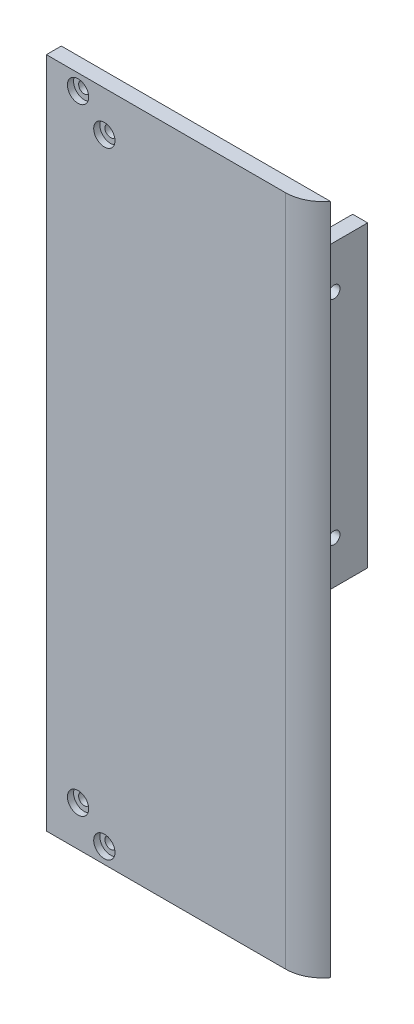
SolidWorks part; units mm, degrees
ref_plane "Alzado" through (0, 0, 0) normal (0, 0, 1) x (1, 0, 0)
ref_plane "Planta" through (0, 0, 0) normal (0, 1, 0) x (1, 0, 0)
ref_plane "Vista lateral" through (0, 0, 0) normal (1, 0, 0) x (0, 0, -1)
sketch "Croquis1" plane through (0, 0, 0) normal (0, 0, 1) x (1, 0, 0)
  line L1 (-4, 72.7734) -> (68, 72.7734)
  line L2 (-4, 72.7734) -> (-4, 252.7734)
  line L3 (-4, 252.7734) -> (68, 252.7734)
  line L4 (68, 72.7734) -> (68, 252.7734)
  line L5 (-4, 72.7734) -> (68, 252.7734) construction
  line L6 (-4, 252.7734) -> (68, 72.7734) construction
  circle A0 centre (4.48, 248.5734) radius 1.5 construction
  circle A1 centre (11.52, 241.9734) radius 1.5 construction
  circle A2 centre (11.52, 76.9734) radius 1.5 construction
  circle A3 centre (4.48, 83.5734) radius 1.5 construction
  circle A4 centre (4.48, 248.5734) radius 1.5
  circle A5 centre (11.52, 241.9734) radius 1.5
  circle A6 centre (11.52, 76.9734) radius 1.5
  circle A7 centre (4.48, 83.5734) radius 1.5
  circle A8 centre (4.48, 248.5734) radius 2.85
  circle A9 centre (11.52, 241.9734) radius 2.85
  circle A10 centre (11.52, 76.9734) radius 2.85
  circle A11 centre (4.48, 83.5734) radius 2.85
  point P4 (32, 162.7734)
  dimension "D1" = 5.7
  dimension "D2" = 5.7
extrude "Saliente-Extruir1" add sketch "Croquis1" along normal blind 4 contours A10 A6 | A11 A7 | L1 L4 L3 L2 A11 A10 A9 A8 | A9 A5 | A8 A4 region at (32.1905, 162.7734, 0) region at (1.7106, 248.5734, 0) region at (8.7506, 241.9734, 0) region at (8.7506, 76.9734, 0) region at (1.7106, 83.5734, 0)
sketch "Croquis2" plane through (0, 0, 4) normal (0, 0, 1) x (1, 0, 0)
  circle A0 centre (4.48, 248.5734) radius 2.85 construction
  circle A1 centre (11.52, 241.9734) radius 2.85 construction
  circle A2 centre (4.48, 83.5734) radius 2.85 construction
  circle A3 centre (11.52, 76.9734) radius 2.85 construction
  circle A4 centre (4.48, 248.5734) radius 2.85
  circle A5 centre (11.52, 241.9734) radius 2.85
  circle A6 centre (4.48, 83.5734) radius 2.85
  circle A7 centre (11.52, 76.9734) radius 2.85
extrude "Cortar-Extruir1" cut sketch "Croquis2" against normal blind 1.65
sketch "Croquis3" plane through (0, 0, 0) normal (0, 0, -1) x (-1, 0, 0)
  line L0 (0, 162.7734) -> (-68, 162.7734) construction
  line L1 (0, 252.7734) -> (0, 72.7734) construction
  line L2 (-68, 72.7734) -> (-68, 252.7734) construction
  line L4 (0, 200.2734) -> (-68, 200.2734) construction
  line L5 (0, 130.2734) -> (-4, 120.2734) construction
  line L6 (0, 205.2734) -> (-4, 205.2734)
  line L7 (0, 205.2734) -> (0, 195.2734)
  line L8 (0, 195.2734) -> (-4, 195.2734)
  line L9 (-4, 205.2734) -> (-4, 195.2734)
  line L10 (0, 205.2734) -> (-4, 195.2734) construction
  line L11 (0, 195.2734) -> (-4, 205.2734) construction
  line L12 (0, 120.2734) -> (-4, 130.2734) construction
  line L13 (0, 125.2734) -> (-68, 125.2734) construction
  line L14 (-4, 120.2734) -> (-4, 130.2734)
  line L15 (0, 130.2734) -> (-4, 130.2734)
  line L16 (0, 120.2734) -> (0, 130.2734)
  line L17 (0, 120.2734) -> (-4, 120.2734)
  point P12 (-2, 200.2734)
  point P19 (-2, 125.2734)
  dimension "D1" = 37.5
  dimension "D2" = 4
  dimension "D3" = 5
  dimension "D4" = 5
extrude "Saliente-Extruir2" add sketch "Croquis3" along normal blind 10
sketch "Croquis4" plane through (0, 0, 0) normal (-1, 0, 0) x (0, 0, 1)
  line L1 (0, 195.2734) -> (-10, 195.2734)
  line L2 (0, 195.2734) -> (0, 205.2734)
  line L3 (0, 205.2734) -> (-10, 205.2734)
  line L4 (-10, 195.2734) -> (-10, 205.2734)
  line L5 (0, 195.2734) -> (-10, 205.2734) construction
  line L6 (0, 205.2734) -> (-10, 195.2734) construction
  line L7 (0, 120.2734) -> (-10, 120.2734)
  line L8 (0, 120.2734) -> (0, 130.2734)
  line L9 (0, 130.2734) -> (-10, 130.2734)
  line L10 (-10, 120.2734) -> (-10, 130.2734)
  line L11 (0, 120.2734) -> (-10, 130.2734) construction
  line L12 (0, 130.2734) -> (-10, 120.2734) construction
  line L13 (-3.3257, 122.3734) -> (-1.6514, 125.2734)
  line L14 (-1.6514, 125.2734) -> (-3.3257, 128.1734)
  line L15 (-3.3257, 128.1734) -> (-6.6743, 128.1734)
  line L16 (-6.6743, 128.1734) -> (-8.3486, 125.2734)
  line L17 (-8.3486, 125.2734) -> (-6.6743, 122.3734)
  line L18 (-6.6743, 122.3734) -> (-3.3257, 122.3734)
  line L19 (-3.3257, 197.3734) -> (-1.6514, 200.2734)
  line L20 (-1.6514, 200.2734) -> (-3.3257, 203.1734)
  line L21 (-3.3257, 203.1734) -> (-6.6743, 203.1734)
  line L22 (-6.6743, 203.1734) -> (-8.3486, 200.2734)
  line L23 (-8.3486, 200.2734) -> (-6.6743, 197.3734)
  line L24 (-6.6743, 197.3734) -> (-3.3257, 197.3734)
  circle A0 centre (-5, 200.2734) radius 1.5
  circle A1 centre (-5, 125.2734) radius 1.5
  circle A2 centre (-5, 125.2734) radius 2.9 construction
  circle A3 centre (-5, 200.2734) radius 2.9 construction
  point P4 (-5, 200.2734)
  point P13 (-5, 125.2734)
  dimension "D1" = 5.8
  dimension "D2" = 3
  dimension "D4" = 3
  dimension "D3" = 5.8
extrude "Cortar-Extruir2" cut sketch "Croquis4" against normal up to next contours A1 | A0 region at (0, 200.2734, -5) region at (0, 125.2734, -5)
extrude "Cortar-Extruir3" cut sketch "Croquis4<3>" against normal blind 1.65 contours L23 L24 L19 L20 L21 L22 A0 | L17 L18 L13 L14 L15 L16 A1 region at (0, 122.462, -5) region at (0, 197.462, -5)
sketch "Croquis4<3>" plane through (0, 0, 0) normal (-1, 0, 0) x (0, 0, 1) same geometry as "Croquis4"
fillet "Redondeo3" radius 10 1 edges at (68, 162.7734, 4)
sketch "Croquis5" plane through (0, 0, 0) normal (0, 0, -1) x (-1, 0, 0)
  line L0 (-68, 72.7734) -> (-68, 252.7734) construction
  line L6 (-28, 202.7734) -> (-24, 202.7734)
  line L7 (4, 162.7734) -> (-68, 162.7734) construction
  line L8 (4, 72.7734) -> (4, 252.7734) construction
  line L9 (-28, 202.7734) -> (-28, 122.7734)
  line L10 (-28, 122.7734) -> (-24, 122.7734)
  line L11 (-24, 202.7734) -> (-24, 122.7734)
  line L12 (-28, 202.7734) -> (-24, 122.7734) construction
  line L13 (-28, 122.7734) -> (-24, 202.7734) construction
  point P0 (-26, 162.7734)
  dimension "D1" = 80
  dimension "D2" = 4
  dimension "D3" = 40
extrude "Saliente-Extruir3" add sketch "Croquis5" along normal blind 50
sketch "Croquis6" plane through (0, 202.7734, 0) normal (0, 1, 0) x (1, 0, 0)
  line L0 (28, 0) -> (33, 0)
  line L1 (28, 0) -> (28, 10)
  line L2 (28, 50) -> (28, 0) construction
  line L3 (28, 10) -> (33, 0)
  dimension "D1" = 11.1803
  dimension "D2" = 5
extrude "Saliente-Extruir4" add sketch "Croquis6" against normal blind 5
sketch "Croquis7" plane through (0, 122.7734, 0) normal (0, -1, 0) x (1, 0, 0)
  line L0 (28, 0) -> (33, 0)
  line L1 (28, 0) -> (28, -10)
  line L2 (28, -50) -> (28, 0) construction
  line L3 (28, -10) -> (33, 0)
  dimension "D1" = 5
  dimension "D2" = 11.1803
extrude "Saliente-Extruir5" add sketch "Croquis7" against normal blind 5
sketch "Croquis9" plane through (24, 0, 0) normal (-1, 0, 0) x (0, 0, 1)
  line L0 (-50, 162.7734) -> (0, 162.7734) construction
  line L1 (-50, 122.7734) -> (-50, 202.7734) construction
  line L2 (0, 122.7734) -> (0, 202.7734) construction
  line L4 (-45, 130.2734) -> (-5, 130.2734) construction
  line L5 (-45, 130.2734) -> (-45, 195.2734) construction
  line L6 (-45, 195.2734) -> (-5, 195.2734) construction
  line L7 (-5, 130.2734) -> (-5, 195.2734) construction
  line L8 (-45, 130.2734) -> (-5, 195.2734) construction
  line L9 (-45, 195.2734) -> (-5, 130.2734) construction
  circle A0 centre (-9, 191.2734) radius 1.6
  circle A1 centre (-41, 191.2734) radius 1.6
  circle A2 centre (-41, 134.2734) radius 1.6
  circle A3 centre (-9, 134.2734) radius 1.6
  point P6 (-25, 162.7734)
  dimension "D1" = 40
  dimension "D3" = 3.2
  dimension "D6" = 3.2
  dimension "D2" = 65
  dimension "D4" = 4
  dimension "D5" = 4
  dimension "D7" = 4
  dimension "D8" = 4
extrude "Cortar-Extruir4" cut sketch "Croquis9" against normal up to next
